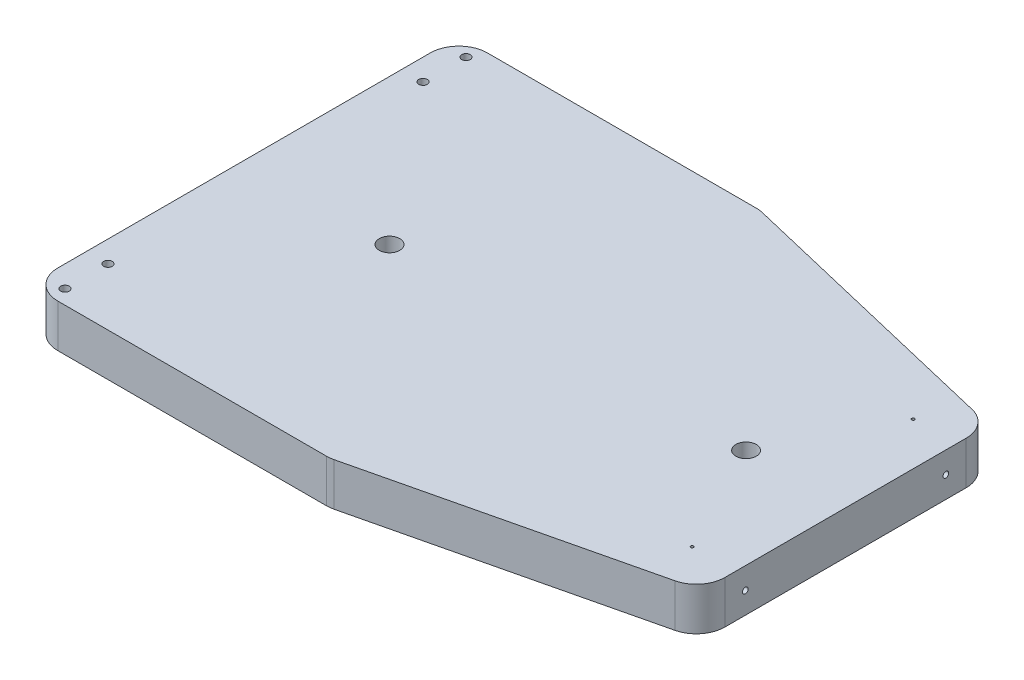
SolidWorks part; units mm, degrees
material "Carvalho"
ref_plane "Plano frontal" through (0, 0, 0) normal (0, 0, 1) x (1, 0, 0)
ref_plane "Plano superior" through (0, 0, 0) normal (0, 1, 0) x (1, 0, 0)
ref_plane "Plano direito" through (0, 0, 0) normal (1, 0, 0) x (0, 0, -1)
sketch "Esboço1" plane through (0, 0, 0) normal (0, 1, 0) x (1, 0, 0)
  line L0 (210, 50) -> (105, 75)
  line L1 (0, -75) -> (105, -75)
  line L2 (0, -75) -> (0, 75)
  line L3 (0, 75) -> (105, 75)
  line L4 (210, -50) -> (210, 50)
  line L5 (195, -38.5714) -> (210, -38.5714) construction
  line L6 (195, -38.5714) -> (195, -53.5714) construction
  line L7 (105, -75) -> (210, -50)
  line L8 (-14.8259, 0) -> (14.392, 0) construction
  line L9 (0, 21.2472) -> (0, -16.7598) construction
  circle A0 centre (50.8, 0) radius 3.5719
  circle A1 centre (175.26, 0) radius 3.57
  circle A2 centre (7.5, -70) radius 1.5
  circle A3 centre (7.5, -55) radius 1.5
  circle A4 centre (7.5, 55) radius 1.5
  circle A5 centre (7.5, 70) radius 1.5
  circle A6 centre (195, -38.5714) radius 0.5
  circle A7 centre (195, 38.5714) radius 0.5
  point P0 (0, 0)
  dimension "D3" = 7.1437
  dimension "D5" = 7.14
  dimension "D9" = 1
  dimension "D1" = 25
  dimension "D2" = 150
  dimension "D4" = 50.8
  dimension "D6" = 210
  dimension "D7" = 175.26
  dimension "D8" = 105
  dimension "D10" = 15
  dimension "D11" = 15
extrude "Ressalto-extrusão1" add sketch "Esboço1" along normal blind 15
sketch "Esboço2" plane through (210, 0, 0) normal (1, 0, 0) x (0, 0, -1)
  line L0 (0, 0) -> (0, 15) construction
  line L1 (-50, 0) -> (50, 0) construction
  line L2 (-50, 15) -> (50, 15) construction
  circle A0 centre (-35, 7.5) radius 1
  circle A1 centre (35, 7.5) radius 1
  point P8 (0, 7.5)
  dimension "D2" = 2
  dimension "D1" = 35
extrude "Corte-extrusão1" cut sketch "Esboço2" against normal blind 10
fillet "Filete1" radius 10 6 edges at (0, 7.5, 75) (105, 7.5, 75) (210, 7.5, 50) (210, 7.5, -50) (0, 7.5, -75) (105, 7.5, -75)
